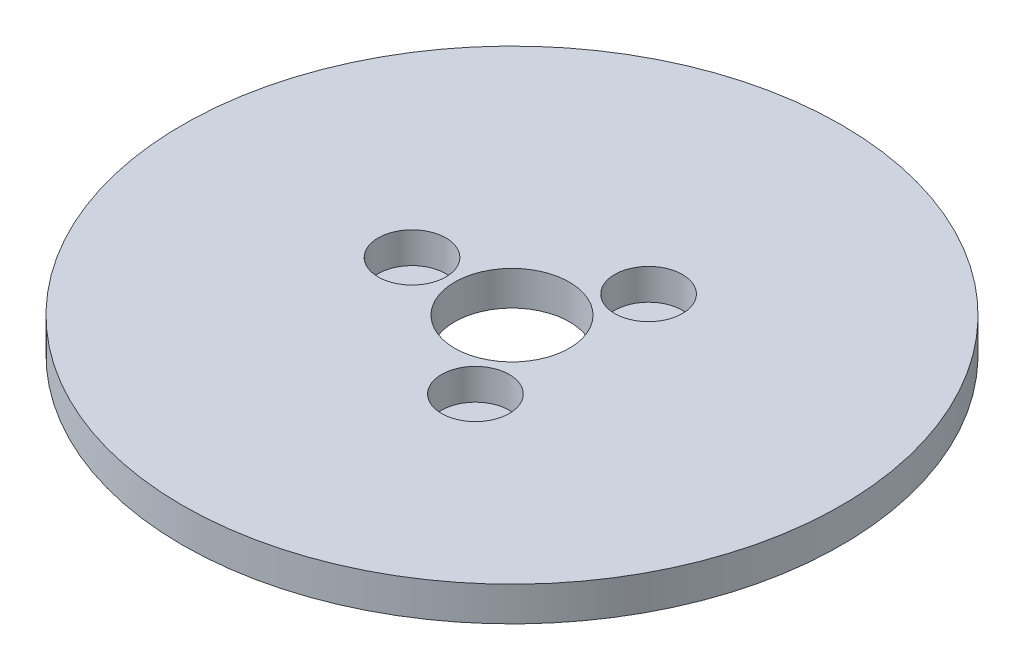
SolidWorks part; units mm, degrees
ref_plane "Front Plane" through (0, 0, 0) normal (0, 0, 1) x (1, 0, 0)
ref_plane "Top Plane" through (0, 0, 0) normal (0, 1, 0) x (1, 0, 0)
ref_plane "Right Plane" through (0, 0, 0) normal (1, 0, 0) x (0, 0, -1)
sketch "Sketch1" plane through (0, 0, 0) normal (0, 1, 0) x (1, 0, 0)
  circle A0 centre (0, 0) radius 57.5
  dimension "FLANGE_OD" = 115
extrude "Boss-Extrude1" add sketch "Sketch1" along normal blind 6
sketch "Sketch2" plane through (0, 0, 0) normal (0, 1, 0) x (1, 0, 0)
  circle A0 centre (0, 0) radius 10
  dimension "BORE_D" = 20
extrude "Cut-Extrude1" cut sketch "Sketch2" along normal through all
sketch "Sketch3" plane through (0, 6, 0) normal (0, 1, 0) x (1, 0, 0)
  circle A0 centre (0, 0) radius 17.443 construction
  circle A1 centre (-17.443, 0) radius 5.907
  dimension "BOLT_D" = 11.8141
  dimension "BOLT_PCD" = 34.886
extrude "Cut-Extrude2" cut sketch "Sketch3" against normal blind 5.4108
pattern_circular "CirPattern1" count 3 over 360 about axis through (0, 0, 0) along (0, 1, 0) of "Cut-Extrude2"
